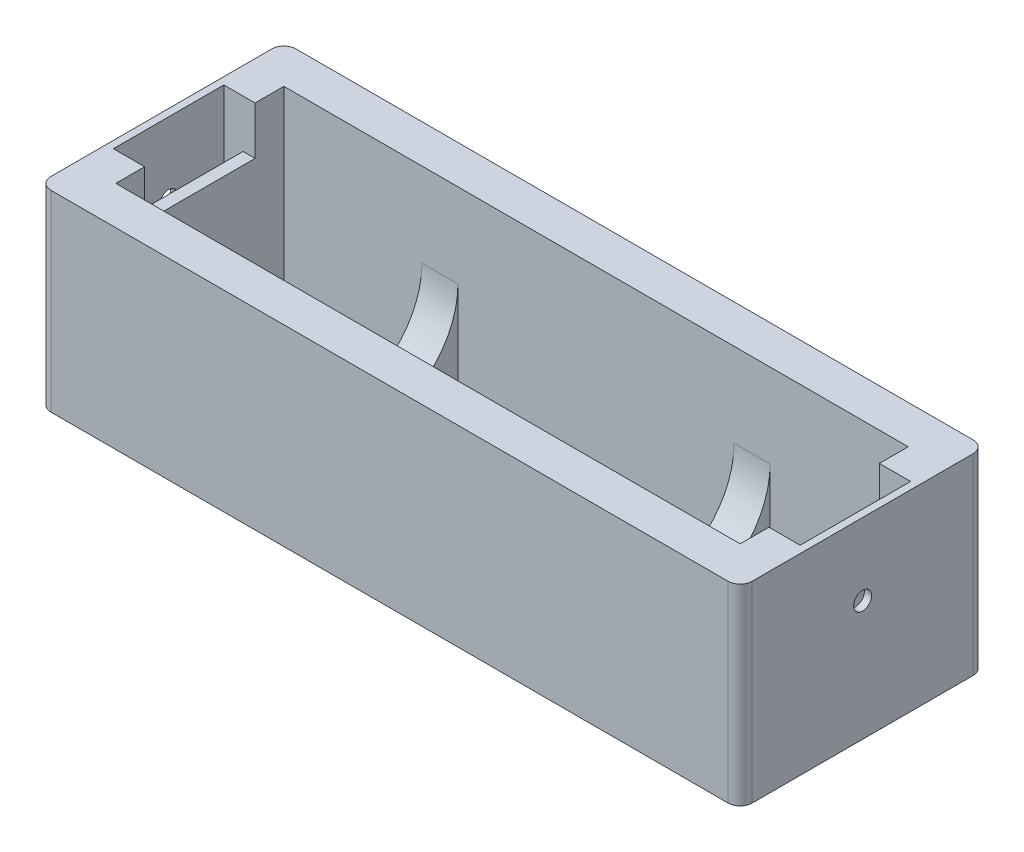
SolidWorks part; units mm, degrees
ref_plane "Front Plane" through (0, 0, 0) normal (0, 0, 1) x (1, 0, 0)
ref_plane "Top Plane" through (0, 0, 0) normal (0, 1, 0) x (1, 0, 0)
ref_plane "Right Plane" through (0, 0, 0) normal (1, 0, 0) x (0, 0, -1)
sketch "Sketch2" plane through (0, 0, 0) normal (0, 1, 0) x (1, 0, 0)
  line L1 (-29.2, -10.2) -> (29.2, -10.2)
  line L2 (-29.2, -10.2) -> (-29.2, 10.2)
  line L3 (-29.2, 10.2) -> (29.2, 10.2)
  line L4 (29.2, -10.2) -> (29.2, 10.2)
  line L5 (-29.2, -10.2) -> (29.2, 10.2) construction
  line L6 (-29.2, 10.2) -> (29.2, -10.2) construction
  point P0 (0, 0)
  dimension "D1" = 58.4
  dimension "D2" = 20.4
extrude "Boss-Extrude1" add sketch "Sketch2" along normal blind 16
sketch "Sketch3" plane through (0, 16, 0) normal (0, 1, 0) x (1, 0, 0)
  line L0 (29.2, -10.2) -> (29.2, 10.2) construction
  line L1 (-26, 7) -> (26, 7)
  line L2 (-26, 7) -> (-26, -7)
  line L3 (-26, -7) -> (26, -7)
  line L4 (26, 7) -> (26, -7)
  line L5 (-26, 7) -> (26, -7) construction
  line L6 (-26, -7) -> (26, 7) construction
  line L7 (-29.2, -10.2) -> (29.2, -10.2) construction
  point P0 (0, 0)
  dimension "D1" = 3.2
  dimension "D2" = 3.2
extrude "Cut-Extrude1" cut sketch "Sketch3" against normal offset from surface (14 mm away) 2 up to face at (0, 0, 0)
fillet "Fillet1" radius 1 4 edges at (-29.2, 8, -10.2) (29.2, 8, -10.2) (29.2, 8, 10.2) (-29.2, 8, 10.2)
sketch "Sketch4" plane through (0, 16, 0) normal (0, 1, 0) x (1, 0, 0)
  line L0 (-26, 7) -> (-26, -7) construction
  line L1 (-26, 0) -> (-27, 0)
  line L2 (-26, 0) -> (-26, 4.6)
  line L3 (-26, 4.6) -> (-27, 4.6)
  line L4 (-27, 0) -> (-27, 4.6)
  dimension "D2" = 4.6
extrude "Cut-Extrude2" cut sketch "Sketch4" against normal offset from surface (4 mm away) 4 up to face at (0, 16, 0)
sketch "Sketch5" plane through (0, 16, 0) normal (0, 1, 0) x (1, 0, 0)
  line L1 (-27, 0) -> (-28.6, 0)
  line L2 (-27, 0) -> (-27, 4.6)
  line L3 (-27, 4.6) -> (-28.6, 4.6)
  line L4 (-28.6, 0) -> (-28.6, 4.6)
  dimension "D2" = 4.6
extrude "Cut-Extrude3" cut sketch "Sketch5" against normal offset from surface (12 mm away) 12 up to face at (-13.25, 16, -1.15)
mirror "Mirror4" about plane through (0, 0, 0) normal (1, 0, 0) of "Cut-Extrude3", "Cut-Extrude2"
mirror "Mirror5" about plane through (0, 0, 0) normal (0, 0, 1) of "Mirror4"
sketch "Sketch6" plane through (29.2, 0, 0) normal (1, 0, 0) x (0, 0, -1)
  line L0 (-9.2, 0) -> (9.2, 0) construction
  circle A0 centre (0, 10) radius 0.75
  dimension "D1" = 1.5
  dimension "D2" = 10
extrude "Cut-Extrude4" cut sketch "Sketch6" against normal up to next
mirror "Mirror6" about plane through (0, 0, 0) normal (1, 0, 0) of "Cut-Extrude4"
ref_plane "Plane1" through (-13, 0, 0) normal (1, 0, 0) x (0, 0, -1)
sketch "Sketch7" plane through (-13, 0, 0) normal (1, 0, 0) x (0, 0, -1)
  line L0 (-7, 2) -> (7, 2) construction
  line L1 (7, 2) -> (7, 16) construction
  line L3 (-7, 2) -> (-7, 16) construction
  circle A0 centre (0, 9) radius 7
sketch "Sketch8" plane through (0, 2, 0) normal (0, 1, 0) x (1, 0, 0)
  line L0 (-13, -7) -> (-13, 7) construction
  line L1 (-14.5, -7) -> (-11.5, -7)
  line L2 (-14.5, -7) -> (-14.5, 7)
  line L3 (-14.5, 7) -> (-11.5, 7)
  line L4 (-11.5, -7) -> (-11.5, 7)
  line L5 (-14.5, -7) -> (-11.5, 7) construction
  line L6 (-14.5, 7) -> (-11.5, -7) construction
  line L7 (26, 7) -> (-26, 7) construction
  point P0 (-13, 0)
extrude "Boss-Extrude2" add sketch "Sketch8" along normal blind 7
extrude "Cut-Extrude5" cut sketch "Sketch7" against normal up to next and the other way up to next contours A0
mirror "Mirror7" about plane through (0, 0, 0) normal (1, 0, 0) of "Cut-Extrude5", "Boss-Extrude2"
equation "\"D1@Sketch2\" = 44 + 6.4 + 8"
equation "\"D2@Sketch2\" = 10 + 6.4 + 4"
equation "\"D1@Boss-Extrude1\" = 10 + 2 + 4"
equation "\"D1@Sketch3\"= 3.2"
equation "\"D2@Sketch3\"=3.2"
equation "\"D1@Cut-Extrude1\"=2"
equation "\"D1@Fillet1\"=1"
equation "\"D2@Sketch4\"=4.6"
equation "\"D1@Sketch5\"=1.6"
equation "\"D2@Sketch5\"=4.6"
equation "\"D1@Sketch8\"=3"
